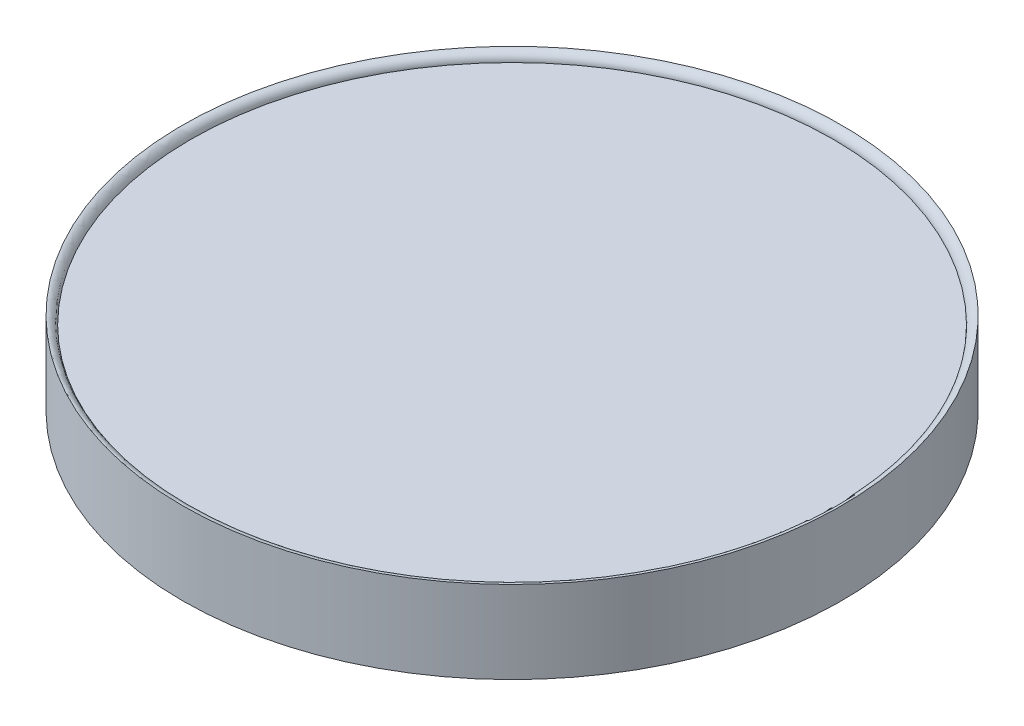
SolidWorks part; units mm, degrees
material "Nylon 101"
ref_plane "Front Plane" through (0, 0, 0) normal (0, 0, 1) x (1, 0, 0)
ref_plane "Top Plane" through (0, 0, 0) normal (0, 1, 0) x (1, 0, 0)
ref_plane "Right Plane" through (0, 0, 0) normal (1, 0, 0) x (0, 0, -1)
sketch "Sketch1" plane through (0, 0, 0) normal (0, 1, 0) x (1, 0, 0)
  circle A0 centre (0, 0) radius 200
extrude "Boss-Extrude1" add sketch "Sketch1" along normal blind 50
sketch "Sketch2" plane through (0, 50, 0) normal (0, 1, 0) x (1, 0, 0)
  circle A0 centre (0, 0) radius 195
extrude "Cut-Extrude1" cut sketch "Sketch2" against normal blind 5 contours A0
fillet "Fillet5" radius 5 1 edges at (0, 50, 195)
